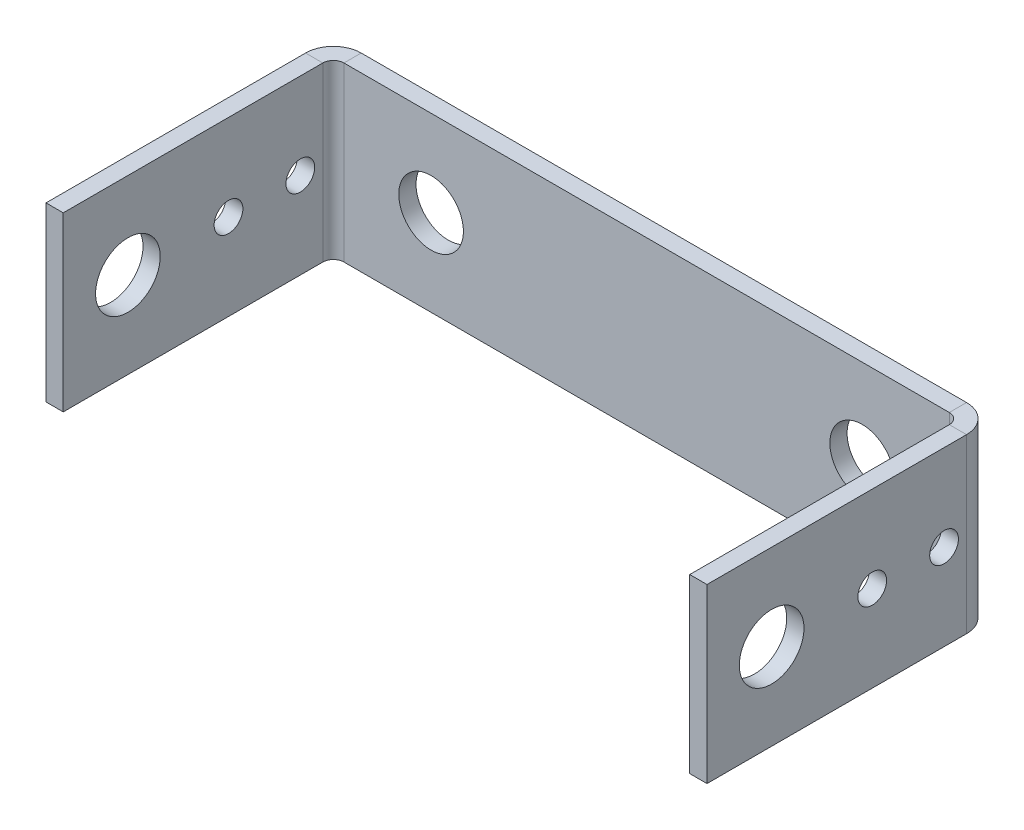
SolidWorks part; units mm, degrees
note: The reader was unsure of these and kept them because the rebuilt part matched: flange length of "Ребро-кромка1".
ref_plane "Спереди" through (0, 0, 0) normal (0, 0, 1) x (1, 0, 0)
ref_plane "Сверху" through (0, 0, 0) normal (0, 1, 0) x (1, 0, 0)
ref_plane "Справа" through (0, 0, 0) normal (1, 0, 0) x (0, 0, -1)
sketch "Эскиз1" plane through (0, 0, 0) normal (0, 0, 1) x (1, 0, 0)
  line L0 (0, 6) -> (46, 6) construction
  line L1 (0, 0) -> (46, 0)
  line L2 (0, 0) -> (0, 12)
  line L3 (0, 12) -> (46, 12)
  line L4 (46, 0) -> (46, 12)
  circle A0 centre (8, 6) radius 2.25
  circle A1 centre (38, 6) radius 2.25
  dimension "D3" = 8
  dimension "D4" = 8
  dimension "D5" = 4.5
  dimension "D1" = 12
  dimension "D2" = 46
base flange "Базовая кромка1" sketch "Эскиз1" thickness 1.2 reverse thickness direction no parameters "D1"=0.7366
edge flange "Ребро-кромка1" sketch "Эскиз10" flange profiles "Эскиз10", "Эскиз11" flange angle 90 flange length 20 flange position material inside bend radius 0.7366 thickness 1.2 relief rectangular parameters "D6"=10, "D8"=1
sketch "Эскиз10" plane through (0, 0, 0) normal (-1, 0, 0) x (0, -1, 0)
  line L2 (-12, 0) -> (-12, 18.8)
  line L3 (-12, 18.8) -> (0, 18.8)
  line L4 (0, 18.8) -> (0, 0)
  line L5 (-12, 0) -> (0, 0) construction
  line L6 (-12, 0) -> (0, 0)
sketch "Эскиз11" plane through (46, 0, 0) normal (1, 0, 0) x (0, 1, 0)
  line L1 (0, 0) -> (12, 0) construction
  line L2 (12, 0) -> (12, 18.8)
  line L3 (12, 18.8) -> (0, 18.8)
  line L4 (0, 18.8) -> (0, 0)
  line L5 (0, 0) -> (12, 0)
bend "EdgeBend1" bend radius 0.7366 bend angle 90 parameters "D5"=1
bend "EdgeBend2" bend radius 0.7366 bend angle 90 parameters "D5"=2
sketch "Эскиз12" plane through (46, 0, 0) normal (1, 0, 0) x (0, 0, -1)
  line L0 (-18.8, 6) -> (1.2, 6) construction
  line L1 (-18.8, 12) -> (-18.8, 0) construction
  line L2 (1.2, 12) -> (1.2, 0) construction
  circle A0 centre (-14.3, 6) radius 2.25
  circle A1 centre (-7.3, 6) radius 1
  circle A2 centre (-2.3, 6) radius 1
  dimension "D1" = 4.5
  dimension "D3" = 5
  dimension "D4" = 7
  dimension "D5" = 2
  dimension "D6" = 2
  dimension "D2" = 15.5
extrude "Вырез-Вытянуть1" cut sketch "Эскиз12" against normal through all normal cut yes
sketch "Сгиб-Линии1" plane through (0, 0, 0) normal (0, 1, 0) x (1, 0, 0)
sketch "Граничная рамка1" plane through (0, 0, 0) normal (0, 1, 0) x (1, 0, 0)
sheet metal parameters "Листовой металл3" thickness 1.2 parameters "D1"=0.7366
flat pattern "Развертка3" [suppressed]
sketch "Сгиб-Линии2" plane through (0, 0, 0) normal (0, 1, 0) x (1, 0, 0)
sketch "Граничная рамка2" [suppressed] plane through (0, 0, 0) normal (0, 1, 0) x (1, 0, 0)
sheet metal parameters "Листовой металл4" thickness 1.2 parameters "D1"=0.7366
flat pattern "Развертка3" [suppressed]
sketch "Сгиб-Линии2" plane through (0, 0, 0) normal (0, 1, 0) x (1, 0, 0)
sketch "Граничная рамка2" [suppressed] plane through (0, 0, 0) normal (0, 1, 0) x (1, 0, 0)
bend of the flat pattern "Плоское состояние-<EdgeBend1>1"
bend of the flat pattern "Плоское состояние-<EdgeBend2>1"
sheet metal parameters "Листовой металл5" thickness 1.2 parameters "D1"=0.7366
flat pattern "Развертка3" [suppressed]
sketch "Сгиб-Линии2" plane through (0, 0, 0) normal (0, 1, 0) x (1, 0, 0)
sketch "Граничная рамка2" [suppressed] plane through (0, 0, 0) normal (0, 1, 0) x (1, 0, 0)
bend of the flat pattern "Плоское состояние-<EdgeBend1>1"
bend of the flat pattern "Плоское состояние-<EdgeBend2>1"
